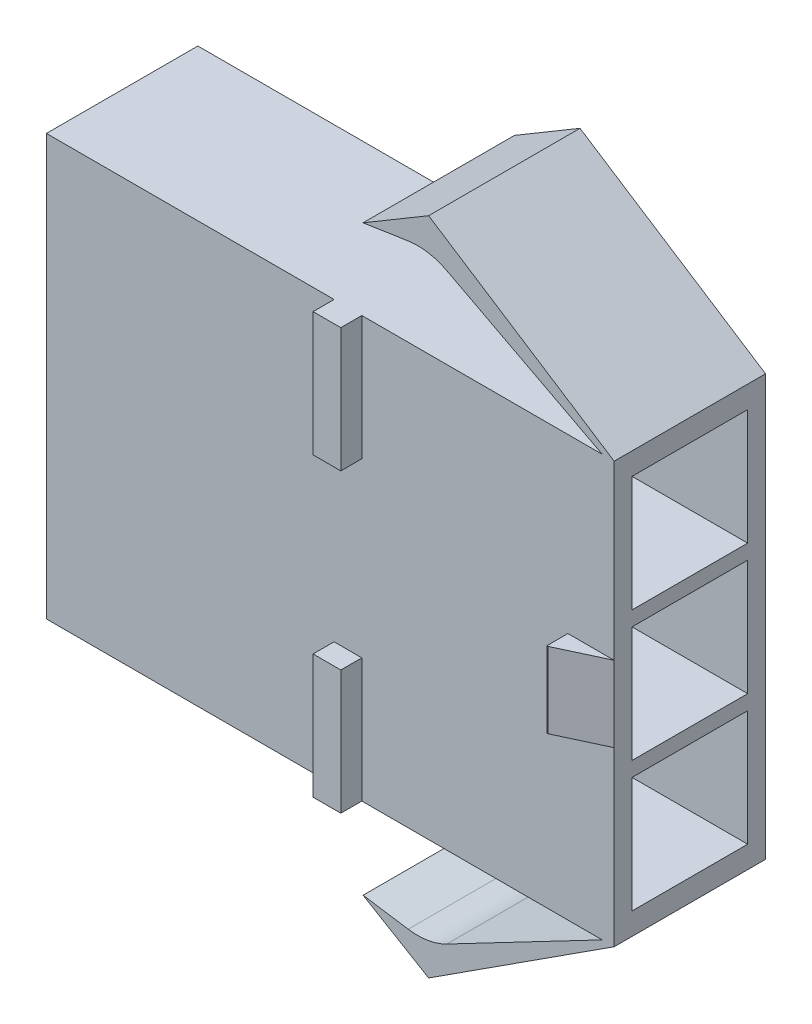
SolidWorks part; units mm, degrees
ref_plane "前视基准面" through (0, 0, 0) normal (0, 0, 1) x (1, 0, 0)
ref_plane "上视基准面" through (0, 0, 0) normal (0, 1, 0) x (1, 0, 0)
ref_plane "右视基准面" through (0, 0, 0) normal (1, 0, 0) x (0, 0, -1)
sketch "草图1" plane through (0, 0, 0) normal (0, 0, 1) x (1, 0, 0)
  line L1 (-13.5, -10) -> (13.5, -10)
  line L2 (-13.5, -10) -> (-13.5, 10)
  line L3 (-13.5, 10) -> (13.5, 10)
  line L4 (13.5, -10) -> (13.5, 10)
  line L5 (-13.5, -10) -> (13.5, 10) construction
  line L6 (-13.5, 10) -> (13.5, -10) construction
  point P0 (0, 0)
  dimension "D1" = 27
  dimension "D2" = 20
extrude "凸台-拉伸1" add sketch "草图1" along normal blind 7.2
sketch "草图2" plane through (13.5, 0, 0) normal (1, 0, 0) x (0, 0, -1)
  line L0 (-7.2, 10) -> (0, -10) construction
  line L1 (0, 10) -> (-7.2, -10) construction
  line L2 (-7.2, -10) -> (-7.2, 10) construction
  line L3 (-6.35, -8.95) -> (-6.35, -3.45)
  line L4 (-6.35, -2.75) -> (-0.85, -2.75)
  line L5 (-6.35, -2.75) -> (-6.35, 2.75)
  line L6 (-6.35, 2.75) -> (-0.85, 2.75)
  line L7 (-0.85, -2.75) -> (-0.85, 2.75)
  line L8 (-6.35, -2.75) -> (-0.85, 2.75) construction
  line L9 (-6.35, 2.75) -> (-0.85, -2.75) construction
  line L10 (-6.35, -3.45) -> (-0.85, -3.45)
  line L11 (-0.85, -8.95) -> (-0.85, -3.45)
  line L12 (-6.35, -8.95) -> (-0.85, -8.95)
  line L13 (-6.35, 8.95) -> (-0.85, 8.95)
  line L14 (-6.35, 3.45) -> (-6.35, 8.95)
  line L15 (-6.35, 3.45) -> (-0.85, 3.45)
  line L16 (-0.85, 3.45) -> (-0.85, 8.95)
  point P9 (-3.6, 0)
  dimension "D1" = 5.5
  dimension "D2" = 5.5
  dimension "D3" = 0.7
  dimension "D4" = 0.7
extrude "切除-拉伸1" cut sketch "草图2" against normal blind 10.2
sketch "草图3" plane through (-13.5, 0, 0) normal (-1, 0, 0) x (0, 0, 1)
  line L0 (7.2, 10) -> (0, -10) construction
  line L1 (7.2, -10) -> (0, 10) construction
  circle A0 centre (3.6, 0) radius 2.75
  circle A1 centre (3.9201, 6.2) radius 2.75
  circle A2 centre (3.6, -6.2) radius 2.75
  dimension "D1" = 5.5
  dimension "D3" = 5.5
  dimension "D2" = 6.2
  dimension "D4" = 6.2
extrude "切除-拉伸2" cut sketch "草图3" against normal blind 18
sketch "草图4" plane through (0, 0, 7.2) normal (0, 0, 1) x (1, 0, 0)
  line L1 (1.5, 10) -> (1.5, 4.1)
  line L2 (13.5, 10) -> (-13.5, 10) construction
  line L3 (13.5, -10) -> (13.5, 10) construction
  line L4 (1.5, 4.1) -> (0.18, 4.1)
  line L6 (0.18, 4.1) -> (0.18, 10)
  line L7 (0.18, 10) -> (1.5, 10)
  line L8 (-13.5, -10) -> (13.5, -10) construction
  line L9 (1.5, -10) -> (0.18, -10)
  line L11 (1.5, -10) -> (1.5, -4.1)
  line L12 (1.5, -4.1) -> (0.18, -4.1)
  line L13 (0.18, -10) -> (0.18, -4.1)
  line L14 (13.5, 0) -> (8.8735, 0) construction
  line L15 (13.5, 1.8) -> (13.5, -1.8)
  line L16 (13.5, -1.8) -> (11.3, -1.8)
  line L18 (13.5, 1.8) -> (11.3, 1.8)
  line L19 (11.3, -1.8) -> (11.3, 1.8)
  dimension "D1" = 12
  dimension "D2" = 1.32
  dimension "D3" = 5.9
  dimension "D4" = 5.9
  dimension "D5" = 3.6
  dimension "D6" = 2.2
extrude "凸台-拉伸2" add sketch "草图4" along normal blind 1
chamfer "倒角1" distance 1 angle 65 1 edges at (13.5, 0, 8.2) first distance on face at (13.5, 6.2, 3.6)
sketch "草图6" plane through (0, 0, 0) normal (0, 0, -1) x (-1, 0, 0)
  line L0 (-13.5, 0) -> (2.3113, 0) construction
  line L1 (-13.5, -10) -> (-13.5, 10) construction
  line L9 (-8.1, -1.6) -> (-8.1, 1.6)
  line L10 (-1.9, -1.6) -> (-8.1, -1.6)
  line L11 (-1.9, -5.9) -> (-1.9, -1.6)
  line L12 (-0.6, -5.9) -> (-1.9, -5.9)
  line L13 (-0.6, 5.9) -> (-0.6, -5.9)
  line L14 (-1.9, 5.9) -> (-0.6, 5.9)
  line L15 (-1.9, 1.6) -> (-1.9, 5.9)
  line L16 (-8.1, 1.6) -> (-1.9, 1.6)
  dimension "D1" = 5.4
extrude "凸台-拉伸4" add sketch "草图6" along normal blind 1
sketch "草图7" plane through (0, 0, 0) normal (0, 0, -1) x (-1, 0, 0)
  line L0 (-13.5, 10) -> (-4.6758, 15.6986)
  line L1 (-4.6758, 15.6986) -> (-1.5586, 13.8477)
  line L2 (-1.5586, 13.8477) -> (-4.6758, 14.3197)
  line L3 (-4.6758, 14.3197) -> (-12.932, 10)
  line L4 (-13.5, 10) -> (13.5, 10) construction
  line L5 (-12.932, 10) -> (-13.5, 10)
  line L6 (-13.5, 0) -> (-10.8611, 0) construction
  line L7 (-13.5, -10) -> (-13.5, 10) construction
  line L8 (-12.932, -10) -> (-13.5, -10)
  line L9 (-4.6758, -14.3197) -> (-12.932, -10)
  line L10 (-1.5586, -13.8477) -> (-4.6758, -14.3197)
  line L11 (-4.6758, -15.6986) -> (-1.5586, -13.8477)
  line L12 (-13.5, -10) -> (-4.6758, -15.6986)
extrude "凸台-拉伸5" add sketch "草图7" against normal blind 7.2
fillet "圆角1" radius 3 1 edges at (4.6758, 14.3197, 3.6)
fillet "圆角2" radius 3 1 edges at (4.6758, -14.3197, 3.6)
sketch "草图8" plane through (-13.5, 0, 0) normal (-1, 0, 0) x (0, 0, 1)
  point P0 (3.9201, 6.2)
  point P1 (3.6, 0)
  point P3 (3.6, -6.2)
sketch "0_0_Point" plane through (-13.5, 0, 0) normal (-1, 0, 0) x (0, 0, 1)
  point P0 (3.9201, 6.2)
other "0_0" parameters "直径"=2, "端头长度"=2
ref_axis "基准轴1" through (-23.5, 6.2, 3.9201) along (1, 0, 0)
sketch "1_0_Point" plane through (-13.5, 0, 0) normal (-1, 0, 0) x (0, 0, 1)
  point P0 (3.6, 0)
other "1_0" parameters "直径"=2, "端头长度"=2
ref_axis "基准轴2" through (-23.5, 0, 3.6) along (1, 0, 0)
sketch "2_0_Point" plane through (-13.5, 0, 0) normal (-1, 0, 0) x (0, 0, 1)
  point P0 (3.6, -6.2)
other "2_0" parameters "直径"=2, "端头长度"=2
ref_axis "基准轴3" through (-23.5, -6.2, 3.6) along (1, 0, 0)
